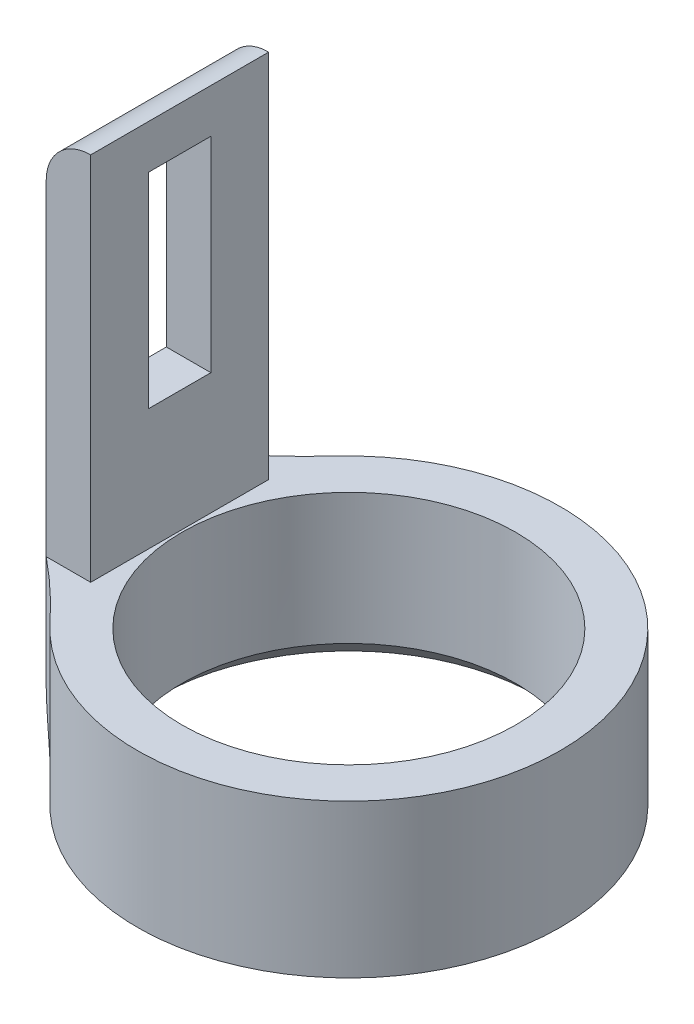
SolidWorks part; units mm, degrees
ref_plane "Front Plane" through (0, 0, 0) normal (0, 0, 1) x (1, 0, 0)
ref_plane "Top Plane" through (0, 0, 0) normal (0, 1, 0) x (1, 0, 0)
ref_plane "Right Plane" through (0, 0, 0) normal (1, 0, 0) x (0, 0, -1)
sketch "Sketch2" plane through (0, 0, 0) normal (0, 1, 0) x (1, 0, 0)
  circle A0 centre (0, 0) radius 4.75
  circle A1 centre (0, 0) radius 3.75
extrude "Boss-Extrude1" add sketch "Sketch2" along normal blind 3.44
ref_plane "Plane1" through (-4.8, 0, 0) normal (1, 0, 0) x (0, 0, -1)
sketch "Sketch3" plane through (-4.8, 0, 0) normal (1, 0, 0) x (0, 0, -1)
  line L0 (0, -0.2424) -> (0, 11.7576) construction
  line L1 (2, 0) -> (2, 11.7576)
  line L2 (-2, 0) -> (-2, 11.7576)
  line L3 (2, 11.7576) -> (-2, 11.7576)
  line L4 (2, -0.2424) -> (2, 11.7576) construction
  line L5 (2, 0) -> (-2, 0)
  line L6 (-4.75, 0) -> (4.75, 0) construction
  line L7 (-2, -0.2424) -> (-2, 11.7576) construction
  dimension "D1" = 2
  dimension "D2" = 2
extrude "Boss-Extrude2" add sketch "Sketch3" along normal blind 1
sketch "Sketch4" plane through (-4.8, 0, 0) normal (-1, 0, 0) x (0, 0, 1)
  line L0 (-0.7, 10.7692) -> (0.7, 10.7692)
  line L2 (0, 10.7692) -> (0, 6.1692) construction
  line L3 (0.7, 6.1692) -> (-0.7, 6.1692)
  line L4 (-0.7, 10.7692) -> (-0.7, 6.1692)
  line L6 (0.7, 10.7692) -> (0.7, 6.1692)
  line L7 (-0.7, 11.7576) -> (-0.7, 10.7692) construction
  line L8 (0, 11.7576) -> (0, 10.7692) construction
  line L9 (0.7, 11.7576) -> (0.7, 10.7692) construction
  dimension "D1" = 0.7
  dimension "D2" = 0.7
extrude "Cut-Extrude1" cut sketch "Sketch4" against normal blind 1
fillet "Fillet1" radius 13 2 edges at (-4.3084, 1.72, 2) (-4.3084, 1.72, -2)
chamfer "Chamfer1" distance 0.5 angle 45 1 edges at (0, 0, 3.75)
fillet "Fillet2" radius 1 2 edges at (-4.8, 0, 0) (-4.8, 11.7576, 0)
